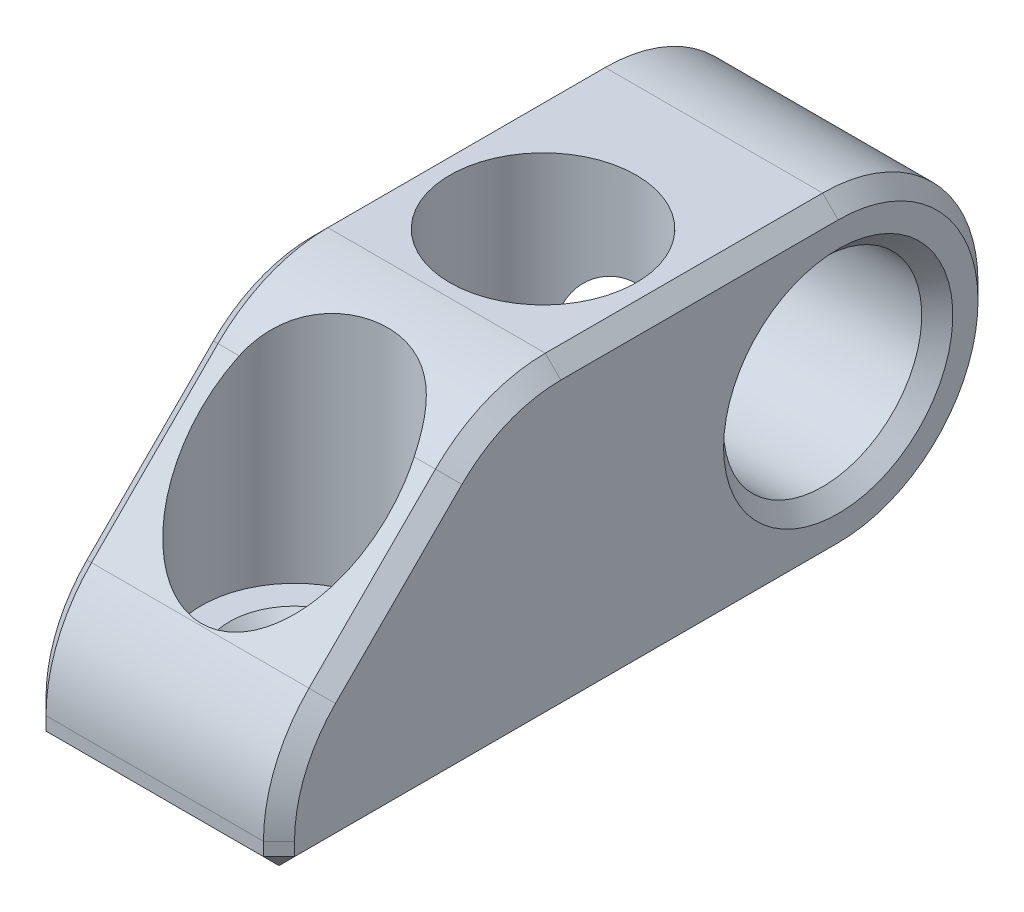
SolidWorks part; units mm, degrees
ref_plane "Front Plane" through (0, 0, 0) normal (0, 0, 1) x (1, 0, 0)
ref_plane "Top Plane" through (0, 0, 0) normal (0, 1, 0) x (1, 0, 0)
ref_plane "Right Plane" through (0, 0, 0) normal (1, 0, 0) x (0, 0, -1)
sketch "Sketch1" plane through (0, 0, 0) normal (0, 1, 0) x (1, 0, 0)
  line L0 (0, 0) -> (0, 1.27) construction
  line L1 (-5.08, -14.605) -> (5.08, -14.605)
  line L2 (-5.08, -14.605) -> (-5.08, 14.605)
  line L3 (-5.08, 14.605) -> (5.08, 14.605)
  line L4 (5.08, -14.605) -> (5.08, 14.605)
  line L5 (-5.08, -14.605) -> (5.08, 14.605) construction
  line L6 (-5.08, 14.605) -> (5.08, -14.605) construction
  line L7 (0, 0) -> (0, -8.89) construction
  circle A0 centre (0, 1.27) radius 2.032
  circle A1 centre (0, -8.89) radius 2.032
  circle A2 centre (0, 1.27) radius 3.81
  circle A3 centre (0, -8.89) radius 3.81
  point P0 (0, 0)
  dimension "D3" = 4.064
  dimension "D6" = 7.62
  dimension "D1" = 29.21
  dimension "D2" = 10.16
  dimension "D4" = 8.89
  dimension "D5" = 1.27
extrude "Boss-Extrude1" add sketch "Sketch1" along normal blind 12.7 contours L1 L4 L3 L2 A1 A0 | A1 | A0 | A2 A0 | A3 A1 region at (-4.7707, 0, 0) region at (0, 0, -1.27) region at (0, 0, 8.89) region at (-3.7022, 0, -1.27) region at (-3.7022, 0, 8.89)
sketch "Sketch2" plane through (-5.08, 0, 0) normal (-1, 0, 0) x (0, 0, 1)
  line L0 (-8.255, 0) -> (-8.255, 6.35) construction
  line L1 (14.605, 0) -> (-14.605, 0) construction
  circle A0 centre (-8.255, 6.35) radius 4.05
  dimension "D1" = 8.1
  dimension "D2" = 6.35
  dimension "D3" = 22.86
extrude "Cut-Extrude1" cut sketch "Sketch2" against normal through all contours A0
extrude "Cut-Extrude2" cut sketch "Sketch1<3>" along normal through all contours A0 | A1 region at (0, 0, -1.27) region at (0, 0, 8.89)
sketch "Sketch1<3>" plane through (0, 0, 0) normal (0, 1, 0) x (1, 0, 0) same geometry as "Sketch1"
extrude "Cut-Extrude3" cut sketch "Sketch1<4>" against normal blind 10.16 from surface contours A3 A1 | A2 A0 region at (-3.7022, 0, -1.27) region at (-3.7022, 0, 8.89) starting at face at (0, 12.7, 0.762)
sketch "Sketch1<4>" plane through (0, 0, 0) normal (0, 1, 0) x (1, 0, 0) same geometry as "Sketch1"
chamfer "Chamfer1" distance 8.89 angle 45 1 edges at (0, 12.7, 14.605)
fillet "Fillet1" radius 6.35 3 edges at (0, 3.81, 14.605) (-3.593, 12.7, 5.715) (3.593, 12.7, 5.715)
chamfer "Chamfer2" distance 0.635 angle 45 2 edges at (-5.08, 6.35, -4.205) (5.08, 6.35, -4.205)
fillet "Fillet2" radius 6.35 2 edges at (0, 0, -14.605) (0, 12.7, -14.605)
chamfer "Chamfer3" distance 0.635 angle 45 2 edges at (0, 0, 10.922) (0, 0, 0.762)
chamfer "Chamfer4" distance 0.635 angle 45 17 edges at (5.08, 0.5899, 14.605) (-5.08, 0.5899, 14.605) (5.08, 3.6098, 14.1216) (-5.08, 3.6098, 14.1216) (5.08, 8.255, 10.16) (-5.08, 8.255, 10.16) (5.08, 12.2166, 5.5148) (-5.08, 12.2166, 5.5148) (5.08, 12.7, -2.5851) (-5.08, 12.7, -2.5851) (0, 0, 14.605) (-5.08, 0, 3.175) (5.08, 0, 3.175) (-5.08, 10.8401, -12.7451) (5.08, 10.8401, -12.7451) (-5.08, 1.8599, -12.7451) (5.08, 1.8599, -12.7451)
chamfer "Chamfer5" distance 0.635 angle 45 2 edges at (0, 2.54, 0.762) (0, 2.54, 10.922)
